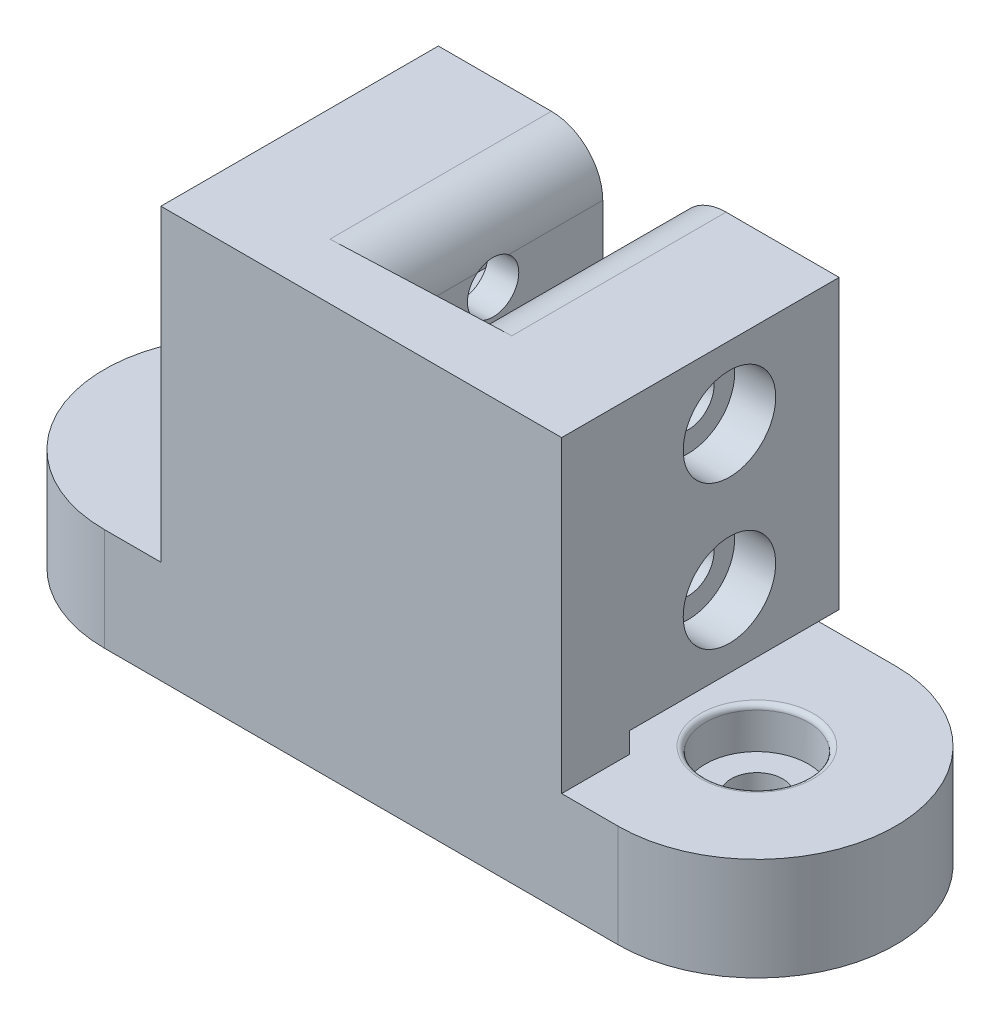
SolidWorks part; units mm, degrees
ref_plane "Alzado" through (0, 0, 0) normal (0, 0, 1) x (1, 0, 0)
ref_plane "Planta" through (0, 0, 0) normal (0, 1, 0) x (1, 0, 0)
ref_plane "Vista lateral" through (0, 0, 0) normal (1, 0, 0) x (0, 0, -1)
sketch "Croquis1" plane through (0, 0, 0) normal (0, 1, 0) x (1, 0, 0)
  line L0 (0, 0) -> (-50, 0) construction
  line L1 (0, -13.5) -> (-50, -13.5)
  line L2 (0, 13.5) -> (-50, 13.5)
  line L3 (-25, 0) -> (-25, 5.9083) construction
  arc A0 (0, -13.5) -> (0, 13.5) centre (0, 0) ccw
  arc A1 (-50, 13.5) -> (-50, -13.5) centre (-50, 0) ccw
  circle A2 centre (-50, 0) radius 2.5
  circle A3 centre (0, 0) radius 2.5
  point P3 (-25, 0)
  dimension "D2" = 50
  dimension "D1" = 27
extrude "Saliente-Extruir1" add sketch "Croquis1" along normal blind 10
sketch "Croquis6" plane through (0, 10, 0) normal (0, 1, 0) x (1, 0, 0)
  line L0 (-50, 0) -> (0, 0) construction
  line L1 (-25, 0) -> (-25, 2.9202) construction
  circle A0 centre (-50, 0) radius 5
  circle A1 centre (0, 0) radius 5
  dimension "D1" = 10
extrude "Cortar-Extruir1" cut sketch "Croquis6" against normal mid plane 8
fillet "Redondeo3" radius 0.5 2 edges at (-50, 10, 5) (0, 10, 5)
sketch "Croquis7" plane through (0, 10, 0) normal (0, 1, 0) x (1, 0, 0)
  line L1 (-44.5, -8.5) -> (-5.5, -6.9)
  line L2 (-44.5, -8.5) -> (-44.5, -13.5)
  line L3 (-44.5, -13.5) -> (-5.5, -13.5)
  line L4 (-5.5, -6.9) -> (-5.5, -13.5)
  line L6 (-50, -13.5) -> (0, -13.5) construction
  circle A0 centre (-50, 0) radius 5.5 construction
  circle A1 centre (0, 0) radius 5.5 construction
  dimension "D1" = 5
extrude "Saliente-Extruir2" add sketch "Croquis7" along normal blind 30
sketch "Croquis8" plane through (0, 40, 0) normal (0, 1, 0) x (1, 0, 0)
  line L0 (-25, -7.7) -> (-25, 13.5) construction
  line L1 (-5.5, -6.9) -> (-44.5, -8.5) construction
  line L2 (-25, 13.5) -> (-28.5, 13.5) construction
  line L3 (-21.5, -8.5) -> (-5.5, -8.5)
  line L4 (-28.5, 13.5) -> (-44.5, 13.5)
  line L5 (-28.5, 13.5) -> (-28.5, -8.5)
  line L6 (-28.5, -8.5) -> (-44.5, -8.5)
  line L7 (-44.5, 13.5) -> (-44.5, -8.5)
  line L8 (-5.5, 13.5) -> (-5.5, -8.5)
  line L9 (-21.5, 13.5) -> (-5.5, 13.5)
  line L10 (-21.5, 13.5) -> (-21.5, -8.5)
  dimension "D1" = 22
  dimension "D2" = 3.5
extrude "Saliente-Extruir3" add sketch "Croquis8" against normal blind 28
sketch "Croquis9" plane through (-5.5, 0, 0) normal (1, 0, 0) x (0, 0, -1)
  line L0 (-7.8436, 12) -> (-7.8436, 40) construction
  line L1 (-7.8436, 12) -> (-7.8436, 40) construction
  line L2 (-7.8436, 40) -> (13.5, 40) construction
  line L3 (13.5, 26) -> (2.8282, 26) construction
  line L4 (13.5, 12) -> (13.5, 40) construction
  line L5 (2.8282, 26) -> (2.8282, 40) construction
  circle A1 centre (2.8282, 33) radius 4.5
  circle A2 centre (2.8282, 19) radius 4.5
  dimension "D1" = 9
extrude "Cortar-Extruir2" cut sketch "Croquis9" against normal blind 4
sketch "Croquis10" plane through (-9.5, 0, 0) normal (1, 0, 0) x (0, 0, -1)
  line L0 (13.5, 26) -> (0.5626, 26) construction
  line L1 (13.5, 12) -> (13.5, 40) construction
  line L2 (2.8282, 33) -> (4.5823, 33) construction
  line L3 (-7.8436, 40) -> (13.5, 40) construction
  line L4 (-7.8436, 40) -> (13.5, 40) construction
  circle A0 centre (2.8282, 33) radius 2.5
  circle A1 centre (2.8282, 19) radius 2.5
  point P11 (0, 0)
  point P12 (2.8282, 40)
  dimension "D1" = 5
extrude "Cortar-Extruir3" cut sketch "Croquis10" against normal up to surface (35 mm away) up to face at (-44.5, 20.6667, 2.8333)
sketch "Croquis11" plane through (-44.5, 0, 0) normal (-1, 0, 0) x (0, 0, 1)
  circle A1 centre (-2.8282, 33) radius 4.5
  circle A2 centre (-2.8282, 19) radius 4.5
  dimension "D1" = 9
  dimension "D2" = 9
extrude "Cortar-Extruir4" cut sketch "Croquis11" against normal blind 4
fillet "Redondeo4" radius 5 2 edges at (-28.5, 40, -2.8282) (-21.5, 40, -2.9718)
sketch "Croquis13" plane through (0, 0, -13.5) normal (0, 0, -1) x (-1, 0, 0)
  line L1 (14.5, 38) -> (18.5, 38)
  line L2 (14.5, 38) -> (14.5, 28)
  line L3 (14.5, 28) -> (18.5, 28)
  line L4 (18.5, 38) -> (18.5, 28)
  line L6 (21.5, 12) -> (21.5, 35) construction
  line L9 (14.5, 24) -> (18.5, 24)
  line L10 (18.5, 14) -> (18.5, 24)
  line L11 (14.5, 14) -> (18.5, 14)
  line L12 (14.5, 14) -> (14.5, 24)
  line L13 (16.5, 40) -> (33.5, 40) construction
  line L14 (16.5, 40) -> (33.5, 40) construction
  line L15 (25, 40) -> (25, 36.8641) construction
  line L16 (35.5, 14) -> (35.5, 24)
  line L17 (35.5, 14) -> (31.5, 14)
  line L18 (31.5, 14) -> (31.5, 24)
  line L19 (35.5, 24) -> (31.5, 24)
  line L20 (35.5, 28) -> (31.5, 28)
  line L21 (31.5, 38) -> (31.5, 28)
  line L22 (35.5, 38) -> (31.5, 38)
  line L23 (35.5, 38) -> (35.5, 28)
  line L25 (28.5, 12) -> (28.5, 35) construction
  dimension "D1" = 10
  dimension "D2" = 4
  dimension "D3" = 3
  dimension "D4" = 4
  dimension "D5" = 4
  dimension "D6" = 10
  dimension "D7" = 10
  dimension "D8" = 3
  dimension "D9" = 3
  dimension "D10" = 4
  dimension "D11" = 10
  dimension "D12" = 3
  dimension "D13" = 4
extrude "Cortar-Extruir6" cut sketch "Croquis13" against normal blind 17
